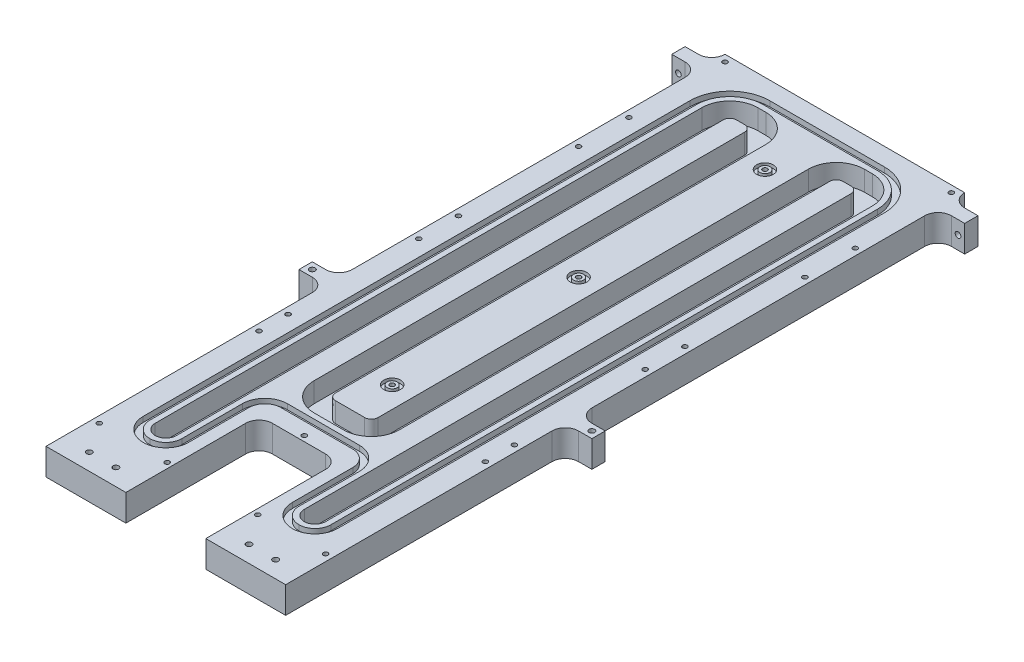
SolidWorks part; units mm, degrees
material "6061 Alloy"
ref_plane "Front Plane" through (0, 0, 0) normal (0, 0, 1) x (1, 0, 0)
ref_plane "Top Plane" through (0, 0, 0) normal (0, 1, 0) x (1, 0, 0)
ref_plane "Right Plane" through (0, 0, 0) normal (1, 0, 0) x (0, 0, -1)
sketch "Sketch1" plane through (0, 0, 0) normal (0, 1, 0) x (1, 0, 0)
  line L0 (-57.15, -171.45) -> (-57.15, 152.4)
  line L1 (-57.15, 152.4) -> (57.15, 152.4)
  line L2 (57.15, 152.4) -> (57.15, -171.45)
  line L3 (57.15, -171.45) -> (19.05, -171.45)
  line L4 (19.05, -171.45) -> (19.05, -107.95)
  line L5 (19.05, -107.95) -> (-19.05, -107.95)
  line L6 (-19.05, -107.95) -> (-19.05, -171.45)
  line L7 (-19.05, -171.45) -> (-57.15, -171.45)
  dimension "D1" = 114.3
  dimension "D2" = 323.85
  dimension "D3" = 38.1
  dimension "D4" = 38.1
  dimension "D5" = 63.5
  dimension "D6" = 57.15
  dimension "D7" = 152.4
extrude "Extrude1" add sketch "Sketch1" along normal blind 12.7
fillet "Fillet1" radius 6.35 1 edges at (-19.05, 6.35, 107.95) type face fillet first side face at (-19.05, 6.35, 139.7) second side face at (0, 6.35, 107.95)
fillet "Fillet2" radius 6.35 1 edges at (19.05, 6.35, 107.95) type face fillet first side face at (3.175, 6.35, 107.95) second side face at (19.05, 6.35, 139.7)
sketch "Sketch7" plane through (57.15, 0, 0) normal (1, 0, 0) x (0, 0, -1)
  line L0 (-171.45, 12.7) -> (152.4, 12.7) construction
  line L2 (152.4, 12.7) -> (152.4, 0) construction
  line L5 (-171.45, 0) -> (152.4, 0) construction
  line L7 (139.7, 12.7) -> (146.05, 12.7)
  line L8 (139.7, 12.7) -> (139.7, 0)
  line L9 (139.7, 0) -> (146.05, 0)
  line L10 (146.05, 12.7) -> (146.05, 0)
  dimension "D1" = 6.35
  dimension "D2" = 6.35
extrude "Extrude2" add sketch "Sketch7" along normal blind 12.7
sketch "Sketch8" plane through (-57.15, 0, 0) normal (-1, 0, 0) x (0, 0, 1)
  line L0 (-152.4, 12.7) -> (171.45, 12.7) construction
  line L1 (-146.05, 12.7) -> (-139.7, 12.7)
  line L2 (-146.05, 12.7) -> (-146.05, 0)
  line L3 (-146.05, 0) -> (-139.7, 0)
  line L4 (-139.7, 12.7) -> (-139.7, 0)
  line L5 (-152.4, 0) -> (171.45, 0) construction
  line L7 (171.45, 12.7) -> (171.45, 0) construction
  line L8 (-152.4, 12.7) -> (-152.4, 0) construction
  dimension "D1" = 6.35
  dimension "D2" = 311.15
  dimension "D3" = 6.35
extrude "Extrude3" add sketch "Sketch8" along normal blind 12.7
fillet "Fillet3" radius 6.35 1 edges type face fillet first side face at (57.15, 7.9375, 93.6625) second side face at (66.675, 7.9375, -139.7)
fillet "Fillet8" radius 6.35 1 edges type face fillet first side face at (-66.675, 4.7625, -139.7) second side face at (-57.15, 4.7625, -61.9125)
sketch "Sketch9" plane through (-57.15, 0, 0) normal (-1, 0, 0) x (0, 0, 1)
  line L0 (-133.35, 12.7) -> (171.45, 12.7) construction
  line L1 (31.75, 12.7) -> (38.1, 12.7)
  line L2 (31.75, 12.7) -> (31.75, 0)
  line L3 (31.75, 0) -> (38.1, 0)
  line L4 (38.1, 12.7) -> (38.1, 0)
  line L5 (-133.35, 0) -> (171.45, 0) construction
  line L6 (171.45, 12.7) -> (171.45, 0) construction
  dimension "D1" = 6.35
  dimension "D2" = 133.35
sketch "Sketch10" plane through (57.15, 0, 0) normal (1, 0, 0) x (0, 0, -1)
  line L0 (-171.45, 12.7) -> (133.35, 12.7) construction
  line L1 (-38.1, 12.7) -> (-31.75, 12.7)
  line L2 (-38.1, 12.7) -> (-38.1, 0)
  line L3 (-38.1, 0) -> (-31.75, 0)
  line L4 (-31.75, 12.7) -> (-31.75, 0)
  line L5 (-171.45, 0) -> (133.35, 0) construction
  line L7 (-171.45, 12.7) -> (-171.45, 0) construction
  dimension "D1" = 6.35
  dimension "D2" = 133.35
extrude "Extrude4" add sketch "Sketch9" along normal blind 12.7
extrude "Extrude5" add sketch "Sketch10" along normal blind 12.7
fillet "Fillet9" radius 6.35 1 edges at (57.15, 6.35, 38.1) type face fillet first side face at (57.15, 6.35, 138.1125) second side face at (63.5, 6.35, 38.1)
fillet "Fillet10" radius 6.35 1 edges at (57.15, 6.35, 31.75) type face fillet first side face at (63.5, 6.35, 31.75) second side face at (57.15, 6.35, -9.525)
fillet "Fillet11" radius 6.35 1 edges at (-57.15, 6.35, 38.1) type face fillet first side face at (-57.15, 6.35, 71.4375) second side face at (-63.5, 6.35, 38.1)
fillet "Fillet12" radius 6.35 1 edges at (-57.15, 6.35, 31.75) type face fillet first side face at (-63.5, 6.35, 31.75) second side face at (-57.15, 6.35, -92.075)
sketch "Sketch11" plane through (0, 12.7, 0) normal (0, 1, 0) x (-1, 0, 0)
  line L0 (69.85, 38.1) -> (63.5, 38.1) construction
  line L1 (69.85, 38.1) -> (69.85, 31.75) construction
  line L2 (-69.85, 38.1) -> (-69.85, 31.75) construction
  line L3 (-69.85, 38.1) -> (-63.5, 38.1) construction
  circle A0 centre (66.675, 34.925) radius 1.016
  circle A1 centre (-66.675, 34.925) radius 1.016
  point P6 (69.85, 34.925)
  point P9 (-69.85, 34.925)
  point P12 (-66.675, 38.1)
  dimension "D1" = 3.175
  dimension "D2" = 3.175
  dimension "D3" = 3.175
  dimension "D4" = 3.175
sketch "Sketch12" plane through (0, 0, -146.05) normal (0, 0, -1) x (-1, 0, 0)
  line L0 (-69.85, 12.7) -> (-69.85, 0) construction
  line L1 (-69.85, 0) -> (-63.5, 0) construction
  line L2 (69.85, 0) -> (57.15, 0) construction
  line L3 (69.85, 12.7) -> (69.85, 0) construction
  circle A0 centre (-66.675, 6.35) radius 1.016
  circle A1 centre (66.675, 6.35) radius 1.016
  point P4 (-69.85, 6.35)
  point P7 (-66.675, 0)
  point P12 (69.85, 6.35)
  dimension "D1" = 3.175
  dimension "D2" = 6.35
  dimension "D3" = 6.35
  dimension "D4" = 3.175
hole_wizard "Tap Drill for #4 Tap1" positions "3DSketch1" profile "Sketch3" hole size "#4-40" standard "Ansi Inch"
sketch3d "3DSketch1"
  line L0 (-57.15, 12.7, -152.4) -> (-57.15, 12.7, -146.05) construction
  line L1 (57.15, 12.7, -152.4) -> (-57.15, 12.7, -152.4) construction
  line L2 (57.15, 12.7, 171.45) -> (57.15, 12.7, 44.45) construction
  line L7 (0, 12.7, -114.3) -> (0, 12.7, 63.5) construction
  line L8 (-19.05, 12.7, 171.45) -> (-19.05, 12.7, 114.3) construction
  line L9 (19.05, 12.7, 114.3) -> (19.05, 12.7, 171.45) construction
  line L10 (-12.7, 12.7, 107.95) -> (12.7, 12.7, 107.95) construction
  point P0 (-53.975, 12.7, -149.225)
  point P2 (53.975, 12.7, -149.225)
  point P4 (53.975, 12.7, 149.225)
  point P6 (21.59, 12.7, 149.225)
  point P8 (0, 12.7, 105.41)
  point P12 (-21.59, 12.7, 149.225)
  point P14 (-53.975, 12.7, 149.225)
  point P16 (-53.975, 12.7, -79.375)
  point P18 (-53.975, 12.7, -3.175)
  point P20 (-53.975, 12.7, 73.025)
  point P22 (53.975, 12.7, 73.025)
  point P24 (53.975, 12.7, -3.175)
  point P26 (53.975, 12.7, -79.375)
  point P28 (0, 12.7, -114.3)
  point P30 (0, 12.7, 63.5)
  point P85 (0, 12.7, -25.4)
  point P88 (0, 12.7, -25.4)
  point P91 (0, 12.7, -25.4)
  dimension "D1" = 3.175
  dimension "D2" = 3.175
  dimension "D3" = 3.175
  dimension "D4" = 69.85
  dimension "D5" = 76.2
  dimension "D6" = 76.2
  dimension "D7" = 76.2
  dimension "D8" = 38.1
  dimension "D13" = 2.54
  dimension "D10" = 2.54
  dimension "D11" = 2.54
  dimension "D12" = 177.8
sketch "Sketch3" plane through (-53.975, 12.7, -149.225) normal (1, 0, 0) x (0, 0, 1)
  line L0 (0, 0) -> (0, 7.0292)
  line L1 (0, 7.0292) -> (1.1303, 6.35)
  line L2 (1.1303, 6.35) -> (1.1303, 0)
  line L5 (1.1303, 0) -> (0, 0)
  line L10 (0, 7.0292) -> (-1.1303, 6.35) construction
  line L11 (0, -6.35) -> (0, 107.95) construction
  dimension "Hole Dia." = 2.2606
  dimension "Hole Depth" = 6.35
  dimension "Drill Angle" = 118
sketch "Sketch13" plane through (0, 12.7, 0) normal (0, 1, 0) x (-1, 0, 0)
  circle A0 centre (0, -114.3) radius 2.3812
  circle A1 centre (0, -114.3) radius 3.9687
  circle A2 centre (0, -25.4) radius 2.3813
  circle A3 centre (0, -25.4) radius 3.9688
  circle A4 centre (0, 63.5) radius 2.3812
  circle A5 centre (0, 63.5) radius 3.9687
  dimension "D1" = 4.7625
  dimension "D2" = 7.9375
extrude "Cut-Extrude6" cut sketch "Sketch13" against normal blind 1.5875
sketch "Sketch14" plane through (0, 0, 0) normal (0, -1, 0) x (1, 0, 0)
  line L3 (-77.3328, -18.025) -> (87.8765, -18.025) construction
  line L4 (57.15, -152.4) -> (-57.15, -152.4) construction
  circle A0 centre (-45, 100.475) radius 1.25
  circle A1 centre (45, 100.475) radius 1.25
  circle A2 centre (-45, -7.525) radius 1.25
  circle A3 centre (0, 63.5) radius 1.1303 construction
  circle A4 centre (45, -7.525) radius 1.25
  circle A5 centre (45, -28.525) radius 1.25
  circle A6 centre (-45, -28.525) radius 1.25
  circle A7 centre (45, -136.525) radius 1.25
  circle A8 centre (-45, -136.525) radius 1.25
  dimension "D3" = 45
  dimension "D4" = 10.5
  dimension "D1" = 108
  dimension "D2" = 90
  dimension "D5" = 15.875
extrude "Cut-Extrude7" cut sketch "Sketch14" against normal blind 6.35
sketch "Sketch16" plane through (0, 12.7, 0) normal (0, 1, 0) x (-1, 0, 0)
  line L0 (57.15, 44.45) -> (57.15, 171.45) construction
  line L1 (20.32, 93.726) -> (-20.32, 93.726)
  line L2 (0, 107.95) -> (0, 171.8025) construction
  line L3 (12.7, 107.95) -> (-12.7, 107.95) construction
  line L5 (40.64, 140.97) -> (40.64, -138.176)
  line L6 (40.64, -138.176) -> (10.16, -138.176)
  line L7 (40.64, 140.97) -> (30.48, 140.97)
  line L8 (30.48, 140.97) -> (30.48, -128.016)
  line L9 (57.15, -133.35) -> (57.15, 25.4) construction
  line L10 (-57.15, -152.4) -> (57.15, -152.4) construction
  line L11 (30.48, -128.016) -> (20.32, -128.016)
  line L12 (20.32, -128.016) -> (20.32, 93.726)
  line L13 (10.16, -138.176) -> (10.16, 83.566)
  line L14 (10.16, 83.566) -> (-10.16, 83.566)
  line L15 (-40.64, -138.176) -> (-10.16, -138.176)
  line L16 (-30.48, -128.016) -> (-20.32, -128.016)
  line L17 (-10.16, -138.176) -> (-10.16, 83.566)
  line L18 (-20.32, -128.016) -> (-20.32, 93.726)
  line L19 (-40.64, 140.97) -> (-30.48, 140.97)
  line L20 (-40.64, 140.97) -> (-40.64, -138.176)
  line L21 (-30.48, 140.97) -> (-30.48, -128.016)
  circle A0 centre (35.56, 134.62) radius 4.7625 construction
  circle A1 centre (-35.56, 134.62) radius 4.7625 construction
  point P32 (0, 83.566)
  point P33 (0, 93.726)
  dimension "D3" = 5.08
  dimension "D1" = 21.59
  dimension "D2" = 287.02
  dimension "D4" = 5.08
  dimension "D5" = 6.35
  dimension "D6" = 16.51
  dimension "D7" = 14.224
  dimension "D8" = 10.16
  dimension "D9" = 10.16
  dimension "D10" = 10.16
  dimension "D11" = 10.16
  dimension "D12" = 14.224
extrude "Cut-Extrude8" cut sketch "Sketch16" against normal blind 9.525
fillet "Fillet13" radius 5.08 4 edges at (40.64, 7.9375, 140.97) (-30.48, 7.9375, 140.97) (30.48, 7.9375, 140.97) (-40.64, 7.9375, 140.97)
fillet "Fillet14" radius 3.175 6 edges at (30.48, 7.9375, -128.016) (-20.32, 7.9375, -128.016) (20.32, 7.9375, -128.016) (-30.48, 7.9375, -128.016) (-10.16, 7.9375, 83.566) (10.16, 7.9375, 83.566)
sketch "Sketch17" plane through (0, 12.7, 0) normal (0, 1, 0) x (-1, 0, 0)
  line L0 (43.18, 143.51) -> (43.18, -140.716)
  line L1 (43.18, -140.716) -> (-43.18, -140.716)
  line L2 (-43.18, -140.716) -> (-43.18, 143.51)
  line L3 (43.18, 143.51) -> (27.94, 143.51)
  line L4 (27.94, 143.51) -> (27.94, 96.266)
  line L5 (27.94, 96.266) -> (-27.94, 96.266)
  line L6 (-27.94, 96.266) -> (-27.94, 143.51)
  line L7 (-27.94, 143.51) -> (-43.18, 143.51)
  line L8 (40.64, -138.176) -> (40.64, 135.89) construction
  line L9 (30.48, 135.89) -> (30.48, -124.841) construction
  line L10 (20.32, 93.726) -> (-20.32, 93.726) construction
  line L11 (-30.48, -124.841) -> (-30.48, 135.89) construction
  line L12 (-40.64, 135.89) -> (-40.64, -138.176) construction
  line L13 (-40.64, -138.176) -> (-10.16, -138.176) construction
  line L14 (46.355, 146.685) -> (24.765, 146.685)
  line L15 (24.765, 146.685) -> (24.765, 99.441)
  line L16 (24.765, 99.441) -> (-24.765, 99.441)
  line L17 (-24.765, 99.441) -> (-24.765, 146.685)
  line L18 (-24.765, 146.685) -> (-46.355, 146.685)
  line L19 (-46.355, 146.685) -> (-46.355, -143.891)
  line L20 (-46.355, -143.891) -> (46.355, -143.891)
  line L21 (46.355, -143.891) -> (46.355, 146.685)
  dimension "D1" = 2.54
  dimension "D2" = 2.54
  dimension "D3" = 2.54
  dimension "D4" = 2.54
  dimension "D5" = 2.54
  dimension "D6" = 2.54
  dimension "D7" = 2.54
  dimension "D8" = 2.54
  dimension "D9" = 3.175
  dimension "D10" = 3.175
  dimension "D11" = 3.175
  dimension "D12" = 3.175
  dimension "D13" = 3.175
  dimension "D14" = 3.175
  dimension "D15" = 3.175
  dimension "D16" = 3.175
extrude "Cut-Extrude9" cut sketch "Sketch17" against normal blind 2.54
fillet "Fillet15" radius 7.62 6 edges at (43.18, 11.43, 143.51) (27.94, 11.43, 143.51) (-27.94, 11.43, 143.51) (-43.18, 11.43, 143.51) (24.765, 11.43, 99.441) (-24.765, 11.43, 99.441)
fillet "Fillet16" radius 10.795 6 edges at (24.765, 11.43, 146.685) (-46.355, 11.43, 146.685) (46.355, 11.43, 146.685) (-24.765, 11.43, 146.685) (27.94, 11.43, 96.266) (-27.94, 11.43, 96.266)
fillet "Fillet17" radius 6.35 2 edges
fillet "Fillet18" radius 13.335 6 edges at (-40.64, 7.9375, -138.176) (10.16, 7.9375, -138.176) (40.64, 7.9375, -138.176) (-10.16, 7.9375, -138.176) (20.32, 7.9375, 93.726) (-20.32, 7.9375, 93.726)
hole_wizard "Tap Drill for #6 Tap1" positions "3DSketch2" profile "Sketch18" hole size "#6-32" standard "Ansi Inch" end condition up to next
sketch3d "3DSketch2"
  point P0 (-66.675, 6.35, -146.05)
  point P3 (66.675, 6.35, -146.05)
  point P13 (-66.675, 12.7, 34.925)
  point P16 (66.675, 12.7, 34.925)
sketch "Sketch18" plane through (-66.675, 6.35, -146.05) normal (1, 0, 0) x (0, 1, 0)
  line L0 (0, 0) -> (0, 6.35)
  line L1 (0, 6.35) -> (1.3525, 6.35)
  line L2 (1.3525, 6.35) -> (1.3525, 0)
  line L5 (1.3525, 0) -> (0, 0)
  line L11 (0, -6.35) -> (0, 107.95) construction
  dimension "Thru Hole Dia." = 2.7051
  dimension "Thru Hole Depth" = 6.35
fillet "Fillet19" radius 15.875 2 edges at (-43.18, 11.43, -140.716) (43.18, 11.43, -140.716)
fillet "Fillet20" radius 19.05 2 edges at (46.355, 11.43, -143.891) (-46.355, 11.43, -143.891)
hole_wizard "Tap Drill for #4 Tap2" positions "3DSketch3" profile "Sketch19" hole size "#4-40" standard "Ansi Inch"
sketch3d "3DSketch3"
  line L0 (57.15, 12.7, -152.4) -> (-57.15, 12.7, -152.4) construction
  line L1 (-57.15, 12.7, -133.35) -> (-57.15, 12.7, 25.4) construction
  line L2 (57.15, 12.7, 25.4) -> (57.15, 12.7, -133.35) construction
  point P0 (-53.975, 12.7, -103.378)
  point P2 (-53.975, 12.7, -22.098)
  point P4 (-53.975, 12.7, 59.182)
  point P6 (53.975, 12.7, 59.182)
  point P8 (53.975, 12.7, -22.098)
  point P10 (53.975, 12.7, -103.378)
  dimension "D1" = 49.022
  dimension "D2" = 3.175
  dimension "D3" = 3.175
  dimension "D4" = 81.28
  dimension "D5" = 81.28
sketch "Sketch19" plane through (-53.975, 12.7, -103.378) normal (1, 0, 0) x (0, 0, 1)
  line L0 (0, 0) -> (0, 7.0292)
  line L1 (0, 7.0292) -> (1.1303, 6.35)
  line L2 (1.1303, 6.35) -> (1.1303, 0)
  line L5 (1.1303, 0) -> (0, 0)
  line L10 (0, 7.0292) -> (-1.1303, 6.35) construction
  line L11 (0, -6.35) -> (0, 107.95) construction
  dimension "Hole Dia." = 2.2606
  dimension "Hole Depth" = 6.35
  dimension "Drill Angle" = 118
hole_wizard "Tap Drill for #6 Tap2" positions "3DSketch4" profile "Sketch20" hole size "#6-32" standard "Ansi Inch" end condition through all
sketch3d "3DSketch4"
  line L0 (-57.15, 12.7, 171.45) -> (-19.05, 12.7, 171.45) construction
  line L1 (-57.15, 12.7, 44.45) -> (-57.15, 12.7, 171.45) construction
  line L2 (-19.05, 12.7, 171.45) -> (-19.05, 12.7, 114.3) construction
  line L3 (19.05, 12.7, 114.3) -> (19.05, 12.7, 171.45) construction
  line L4 (57.15, 12.7, 171.45) -> (57.15, 12.7, 44.45) construction
  line L7 (-57.15, 12.7, 158.75) -> (57.15, 12.7, 158.75) construction
  point P0 (-44.45, 12.7, 163.5125)
  point P2 (-31.75, 12.7, 163.5125)
  point P4 (31.75, 12.7, 163.5125)
  point P6 (44.45, 12.7, 163.5125)
  dimension "D1" = 4.7625
  dimension "D2" = 12.7
  dimension "D3" = 12.7
  dimension "D4" = 12.7
  dimension "D5" = 12.7
  dimension "D6" = 12.7
sketch "Sketch20" plane through (-44.45, 12.7, 163.5125) normal (1, 0, 0) x (0, 0, 1)
  line L0 (0, 0) -> (0, 12.7)
  line L1 (0, 12.7) -> (1.3525, 12.7)
  line L2 (1.3525, 12.7) -> (1.3525, 0)
  line L5 (1.3525, 0) -> (0, 0)
  line L11 (0, -6.35) -> (0, 107.95) construction
  dimension "Thru Hole Dia." = 2.7051
  dimension "Thru Hole Depth" = 12.7
